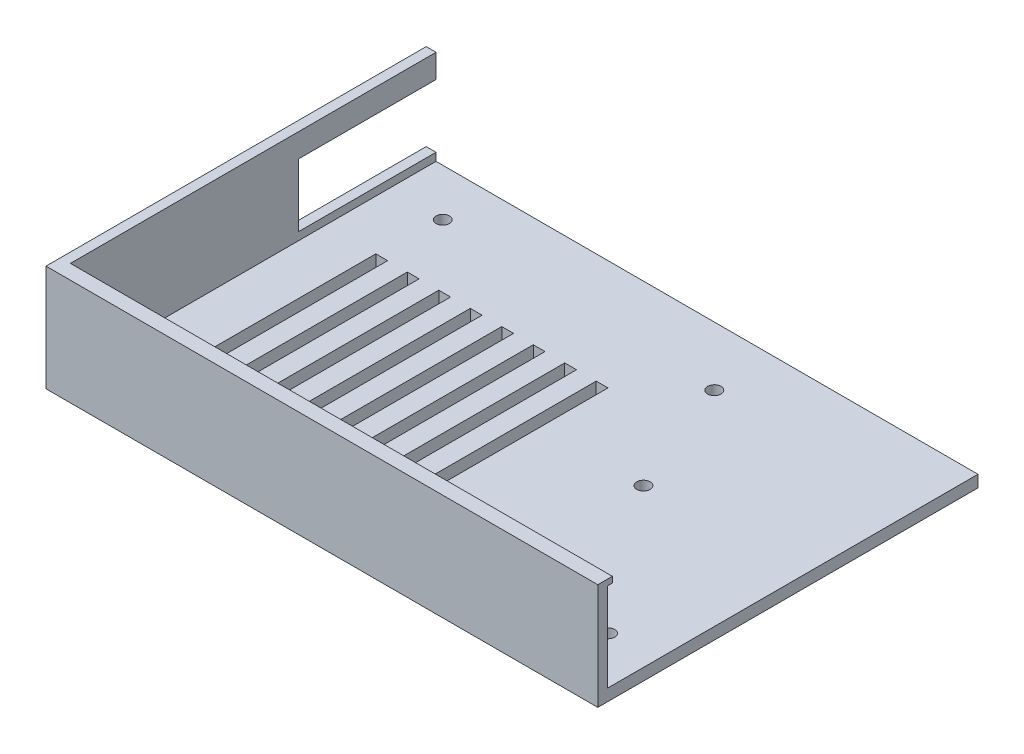
SolidWorks part; units mm, degrees
ref_plane "Front Plane" through (0, 0, 0) normal (0, 0, 1) x (1, 0, 0)
ref_plane "Top Plane" through (0, 0, 0) normal (0, 1, 0) x (1, 0, 0)
ref_plane "Right Plane" through (0, 0, 0) normal (1, 0, 0) x (0, 0, -1)
sketch "Sketch1" plane through (0, 0, 0) normal (0, 1, 0) x (1, 0, 0)
  line L1 (-140.2, -96.6) -> (140.2, -96.6)
  line L2 (-140.2, -96.6) -> (-140.2, 96.6)
  line L3 (-140.2, 96.6) -> (140.2, 96.6)
  line L4 (140.2, -96.6) -> (140.2, 96.6)
  line L5 (-140.2, -96.6) -> (140.2, 96.6) construction
  line L6 (-140.2, 96.6) -> (140.2, -96.6) construction
  dimension "D1" = 280.4
  dimension "D2" = 193.2
extrude "Shell Block" add sketch "Sketch1" along normal blind 27
ref_plane "Shell Front" through (0, 27, 0) normal (0, 1, 0) x (1, 0, 0)
sketch "Sketch2" plane through (0, 27, 0) normal (0, 1, 0) x (1, 0, 0)
  line L1 (-137.7, -92.9) -> (137.7, -92.9)
  line L2 (-137.7, -92.9) -> (-137.7, 92.9)
  line L3 (-137.7, 92.9) -> (137.7, 92.9)
  line L4 (137.7, -92.9) -> (137.7, 92.9)
  line L5 (-137.7, -92.9) -> (137.7, 92.9) construction
  line L6 (-137.7, 92.9) -> (137.7, -92.9) construction
  dimension "D1" = 275.4
  dimension "D2" = 185.8
extrude "Front Opening" cut sketch "Sketch2" against normal blind 1.5
ref_plane "Under Lip" through (0, 25.5, 0) normal (0, 1, 0) x (1, 0, 0)
sketch "Sketch3" plane through (0, 25.5, 0) normal (0, 1, 0) x (1, 0, 0)
  line L1 (-137.7, -94.1) -> (137.7, -94.1)
  line L2 (-137.7, -94.1) -> (-137.7, 94.1)
  line L3 (-137.7, 94.1) -> (137.7, 94.1)
  line L4 (137.7, -94.1) -> (137.7, 94.1)
  line L5 (-137.7, -94.1) -> (137.7, 94.1) construction
  line L6 (-137.7, 94.1) -> (137.7, -94.1) construction
  dimension "D1" = 275.4
  dimension "D2" = 188.2
extrude "Display Pocket" cut sketch "Sketch3" against normal blind 22.5
ref_plane "Back Inner" through (0, 3, 0) normal (0, 1, 0) x (1, 0, 0)
sketch "Sketch4" plane through (0, 3, 0) normal (0, 1, 0) x (1, 0, 0)
  line L1 (-69, 28) -> (-66, 28)
  line L2 (-69, 28) -> (-69, 84)
  line L3 (-69, 84) -> (-66, 84)
  line L4 (-66, 28) -> (-66, 84)
  line L6 (-69, -84) -> (-66, -84)
  line L7 (-69, -84) -> (-69, -28)
  line L8 (-69, -28) -> (-66, -28)
  line L9 (-66, -84) -> (-66, -28)
  line L11 (-77, 28) -> (-74, 28)
  line L12 (-77, 28) -> (-77, 84)
  line L13 (-77, 84) -> (-74, 84)
  line L14 (-74, 28) -> (-74, 84)
  line L16 (-77, -84) -> (-74, -84)
  line L17 (-77, -84) -> (-77, -28)
  line L18 (-77, -28) -> (-74, -28)
  line L19 (-74, -84) -> (-74, -28)
  line L21 (-85, 28) -> (-82, 28)
  line L22 (-85, 28) -> (-85, 84)
  line L23 (-85, 84) -> (-82, 84)
  line L24 (-82, 28) -> (-82, 84)
  line L26 (-85, -84) -> (-82, -84)
  line L27 (-85, -84) -> (-85, -28)
  line L28 (-85, -28) -> (-82, -28)
  line L29 (-82, -84) -> (-82, -28)
  line L31 (-93, 28) -> (-90, 28)
  line L32 (-93, 28) -> (-93, 84)
  line L33 (-93, 84) -> (-90, 84)
  line L34 (-90, 28) -> (-90, 84)
  line L36 (-93, -84) -> (-90, -84)
  line L37 (-93, -84) -> (-93, -28)
  line L38 (-93, -28) -> (-90, -28)
  line L39 (-90, -84) -> (-90, -28)
  line L41 (-101, 28) -> (-98, 28)
  line L42 (-101, 28) -> (-101, 84)
  line L43 (-101, 84) -> (-98, 84)
  line L44 (-98, 28) -> (-98, 84)
  line L46 (-101, -84) -> (-98, -84)
  line L47 (-101, -84) -> (-101, -28)
  line L48 (-101, -28) -> (-98, -28)
  line L49 (-98, -84) -> (-98, -28)
  line L51 (-109, 28) -> (-106, 28)
  line L52 (-109, 28) -> (-109, 84)
  line L53 (-109, 84) -> (-106, 84)
  line L54 (-106, 28) -> (-106, 84)
  line L56 (-109, -84) -> (-106, -84)
  line L57 (-109, -84) -> (-109, -28)
  line L58 (-109, -28) -> (-106, -28)
  line L59 (-106, -84) -> (-106, -28)
  line L61 (-117, 28) -> (-114, 28)
  line L62 (-117, 28) -> (-117, 84)
  line L63 (-117, 84) -> (-114, 84)
  line L64 (-114, 28) -> (-114, 84)
  line L66 (-117, -84) -> (-114, -84)
  line L67 (-117, -84) -> (-117, -28)
  line L68 (-117, -28) -> (-114, -28)
  line L69 (-114, -84) -> (-114, -28)
  line L71 (-125, 28) -> (-122, 28)
  line L72 (-125, 28) -> (-125, 84)
  line L73 (-125, 84) -> (-122, 84)
  line L74 (-122, 28) -> (-122, 84)
  line L76 (-125, -84) -> (-122, -84)
  line L77 (-125, -84) -> (-125, -28)
  line L78 (-125, -28) -> (-122, -28)
  line L79 (-122, -84) -> (-122, -28)
extrude "Vent Slots" cut sketch "Sketch4" against normal blind 4
sketch "Sketch5" plane through (0, 0, 0) normal (1, 0, 0) x (0, 0, -1)
  line L1 (-35, 5) -> (35, 5)
  line L2 (-35, 5) -> (-35, 21)
  line L3 (-35, 21) -> (35, 21)
  line L4 (35, 5) -> (35, 21)
extrude "Cable Exit (-X short side)" cut sketch "Sketch5" against normal blind 141.2
sketch "Sketch6" plane through (0, 3, 0) normal (0, 1, 0) x (1, 0, 0)
  circle A0 centre (-40, -45) radius 1.7
  circle A1 centre (-40, 45) radius 1.7
  circle A2 centre (40, -45) radius 1.7
  circle A3 centre (40, 45) radius 1.7
  circle A4 centre (-52, -15) radius 1.7
  circle A5 centre (-52, 15) radius 1.7
  circle A6 centre (52, -15) radius 1.7
  circle A7 centre (52, 15) radius 1.7
  circle A8 centre (-12, -82) radius 1.7
  circle A9 centre (-12, 82) radius 1.7
  circle A10 centre (12, -82) radius 1.7
  circle A11 centre (12, 82) radius 1.7
  circle A12 centre (-124, -12) radius 1.7
  circle A13 centre (-124, 12) radius 1.7
  circle A14 centre (124, -12) radius 1.7
  circle A15 centre (124, 12) radius 1.7
extrude "Bolt Holes" cut sketch "Sketch6" against normal blind 4
sketch "Sketch7" plane through (0, 0, 0) normal (0, 1, 0) x (1, 0, 0)
  line L1 (200, -200) -> (0, -200)
  line L2 (200, -200) -> (200, 200)
  line L3 (200, 200) -> (0, 200)
  line L4 (0, -200) -> (0, 200)
extrude "Keep one half (X)" cut sketch "Sketch7" against normal through all and the other way through all
sketch "Sketch8" plane through (0, 0, 0) normal (0, 1, 0) x (1, 0, 0)
  line L1 (-200, 0) -> (200, 0)
  line L2 (-200, 0) -> (-200, 200)
  line L3 (-200, 200) -> (200, 200)
  line L4 (200, 0) -> (200, 200)
extrude "Keep one quarter (Z)" cut sketch "Sketch8" against normal through all and the other way through all
equation "\"DispL\"= 274.2"
equation "\"DispW\"= 187.0"
equation "\"DispT\"= 20.0"
equation "\"Clr\"= 0.6"
equation "\"Wall\"= 2.5"
equation "\"BackT\"= 3.0"
equation "\"CableRoom\"= 4.0"
equation "\"LipW\"= 1.2"
equation "\"LipT\"= 1.5"
equation "\"CableW\"= 70.0"
equation "\"CableH\"= 16.0"
equation "\"BoltD\"= 3.4"
equation "\"ShellL\"= \"DispL\" + 2 * \"Clr\" + 2 * \"Wall\""
equation "\"ShellW\"= \"DispW\" + 2 * \"Clr\" + 2 * \"Wall\""
equation "\"ShellH\"= \"BackT\" + \"DispT\" + \"CableRoom\""
equation "\"D1@Sketch1\" = \"ShellL\""
equation "\"D2@Sketch1\" = \"ShellW\""
equation "\"D1@Shell Block\" = \"ShellH\""
equation "\"D1@Shell Front\" = \"ShellH\""
equation "\"D1@Sketch2\" = \"DispL\" + 2 * \"Clr\""
equation "\"D2@Sketch2\" = \"DispW\" + 2 * \"Clr\" - 2 * \"LipW\""
equation "\"D1@Front Opening\" = \"LipT\""
equation "\"D1@Under Lip\" = \"ShellH\" - \"LipT\""
equation "\"D1@Sketch3\" = \"DispL\" + 2 * \"Clr\""
equation "\"D2@Sketch3\" = \"DispW\" + 2 * \"Clr\""
equation "\"D1@Display Pocket\" = \"ShellH\" - \"LipT\" - \"BackT\""
equation "\"D1@Back Inner\" = \"BackT\""
